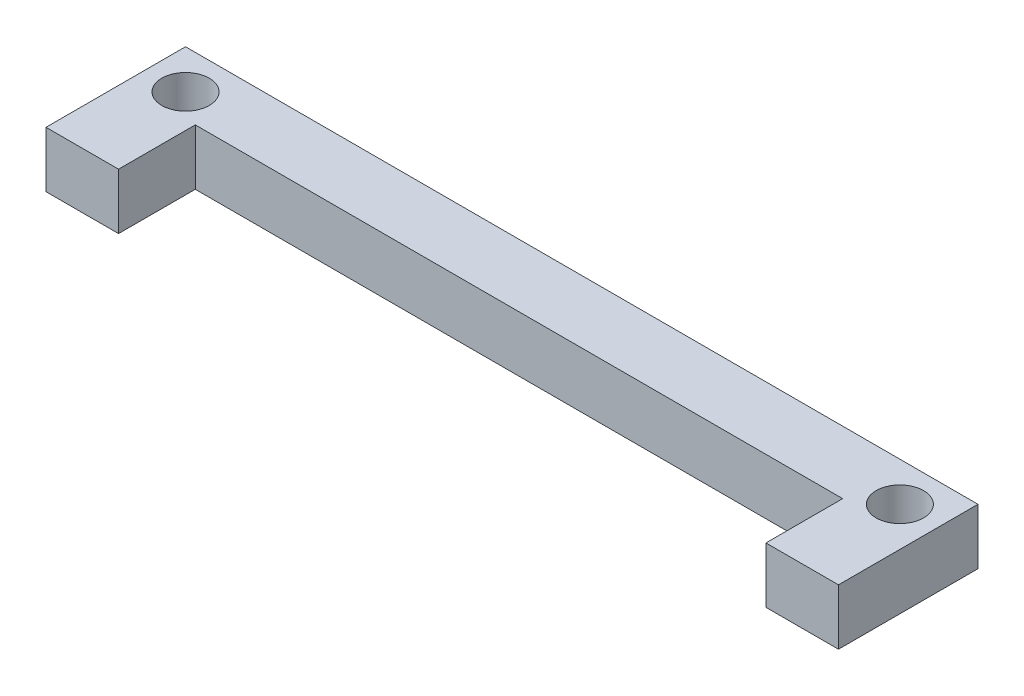
SolidWorks part; units mm, degrees
ref_plane "Front Plane" through (0, 0, 0) normal (0, 0, 1) x (1, 0, 0)
ref_plane "Top Plane" through (0, 0, 0) normal (0, 1, 0) x (1, 0, 0)
ref_plane "Right Plane" through (0, 0, 0) normal (1, 0, 0) x (0, 0, -1)
sketch "Sketch1" plane through (0, 0, 0) normal (0, 1, 0) x (1, 0, 0)
  line L0 (-55, 0) -> (55, 0) construction
  line L1 (-71, 11.25) -> (71, 11.25)
  line L3 (-58, 0) -> (58, 0)
  line L4 (71, 11.25) -> (71, 0)
  line L8 (-71, -13.75) -> (-58, -13.75)
  line L9 (-58, -13.75) -> (-58, 0)
  line L10 (0, -55) -> (0, 55) construction
  line L11 (71, -13.75) -> (58, -13.75)
  line L12 (58, -13.75) -> (58, 0)
  line L13 (71, 0) -> (71, -13.75)
  line L14 (-64, 4.25) -> (-64, 11.25) construction
  line L15 (-64, 4.25) -> (-71, 4.25) construction
  line L19 (-71, 11.25) -> (-71, -13.75)
  circle A0 centre (-64, 4.25) radius 4.25
  circle A1 centre (64, 4.25) radius 4.25
  point P6 (0, 0)
  dimension "D2" = 8.5
  dimension "D1" = 142
  dimension "D3" = 116
  dimension "D4" = 25
  dimension "D5" = 7
extrude "Boss-Extrude1" add sketch "Sketch1" along normal blind 10
